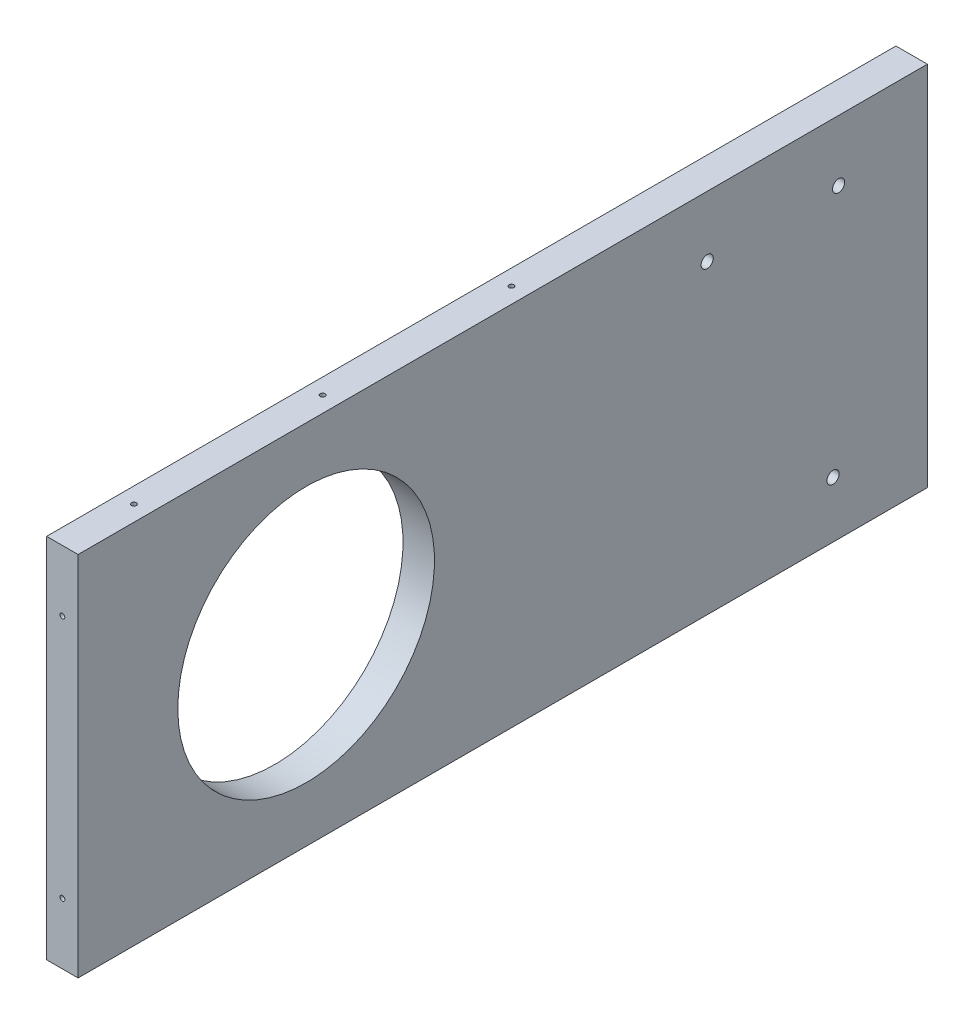
SolidWorks part; units mm, degrees
material "MDF"
ref_plane "Front Plane" through (0, 0, 0) normal (0, 0, 1) x (1, 0, 0)
ref_plane "Top Plane" through (0, 0, 0) normal (0, 1, 0) x (1, 0, 0)
ref_plane "Right Plane" through (0, 0, 0) normal (1, 0, 0) x (0, 0, -1)
sketch "Sketch1" plane through (0, 0, 0) normal (0, 0, 1) x (1, 0, 0)
  line L0 (-272.8912, -3.175) -> (-450.3737, -3.175) construction
  line L1 (-438.8802, -3.175) -> (-451.5802, -3.175)
  line L2 (-438.8802, -3.175) -> (-438.8802, -151.2545)
  line L3 (-438.8802, -151.2545) -> (-451.5802, -151.2545)
  line L4 (-451.5802, -3.175) -> (-451.5802, -151.2545)
  line L6 (-450.3737, -152.2395) -> (-393.0861, -199.0142) construction
  line L8 (-451.5802, -20.574) -> (-451.5802, -45.974) construction
  dimension "D1" = 12.7
extrude "Boss-Extrude1" add sketch "Sketch1" along normal blind 342.9
hole_wizard "15/64 (0.23438) Diameter Hole1" positions "Sketch2" profile "Sketch3" hole size "15/64" standard "ANSI Inch"
sketch "Sketch2" plane through (-183.6737, 1933.3759, -6.35) normal (0, 0, -1) x (1, 0, 0)
  point P0 (-261.5565, 1973.5707)
  point P3 (-261.5565, 2010.5906)
  point P6 (-261.5565, 2047.6104)
  point P9 (-97.5233, 2112.4817)
  point P12 (-97.5233, 2147.6884)
  point P15 (-43.3641, 2120.0659)
  point P18 (1.27, 2120.0659)
  point P21 (45.9041, 2120.0659)
  point P24 (100.0633, 2147.6884)
  point P27 (100.0633, 2112.4817)
  point P30 (264.0965, 2047.6104)
  point P33 (264.0965, 1973.5707)
sketch "Sketch3" plane through (-445.2302, -40.1949, -6.35) normal (1, 0, 0) x (0, 1, 0)
  line L0 (0, 0) -> (0, 14.4885)
  line L1 (0, 14.4885) -> (2.9766, 12.7)
  line L2 (2.9766, 12.7) -> (2.9766, 0)
  line L3 (2.9766, 0) -> (0, 0)
  line L4 (0, 14.4885) -> (-2.9766, 12.7) construction
  line L5 (0, -6.35) -> (0, 107.95) construction
  dimension "Hole Dia." = 5.9533
  dimension "Hole Depth" = 12.7
  dimension "Drill Angle" = 118
hole_wizard "15/64 (0.23438) Diameter Hole3" positions "Sketch6" profile "Sketch7" hole size "15/64" standard "ANSI Inch"
sketch "Sketch6" plane through (-182.4037, 1936.854, -6.35) normal (0, 0, -1) x (1, 0, 0)
  point P0 (-262.8265, 2051.0885)
  point P3 (-262.8265, 2014.0687)
  point P6 (-262.8265, 1977.0488)
  point P9 (-98.7933, 2115.9598)
  point P12 (-98.7933, 2151.1665)
  point P15 (-44.6341, 2123.544)
  point P18 (0, 2123.544)
  point P21 (44.6341, 2123.544)
sketch "Sketch7" plane through (-445.2302, -114.2346, -6.35) normal (1, 0, 0) x (0, 1, 0)
  line L0 (0, 0) -> (0, 20.8385)
  line L1 (0, 20.8385) -> (2.9766, 19.05)
  line L2 (2.9766, 19.05) -> (2.9766, 0)
  line L3 (2.9766, 0) -> (0, 0)
  line L4 (0, 20.8385) -> (-2.9766, 19.05) construction
  line L5 (0, -6.35) -> (0, 107.95) construction
  dimension "Hole Dia." = 5.9533
  dimension "Hole Depth" = 19.05
  dimension "Drill Angle" = 118
hole_wizard "5/64 (0.07813) Diameter Hole1" positions "Sketch8" profile "Sketch9" hole size "5/64" standard "ANSI Inch"
sketch "Sketch8" plane through (-182.4037, 15.875, 6471.4599) normal (0, 1, 0) x (1, 0, 0)
  line L1 (-1.27, 6109.5099) -> (-1.27, 6338.7449) construction
  point P0 (-262.8265, 6157.4524)
  point P6 (-98.7933, 6157.4524)
  point P18 (-262.8265, 6233.6524)
  point P19 (-98.7933, 6233.6524)
  point P22 (-262.8265, 6309.8524)
  point P23 (-98.7933, 6309.8524)
  point P24 (-267.97, 6119.0349)
  point P34 (-115.57, 6119.0349)
  point P37 (-1.27, 6119.0349)
  point P40 (113.03, 6119.0349)
  point P44 (265.43, 6119.0349)
  point P55 (96.2533, 6309.8524)
  point P56 (260.2865, 6309.8524)
  point P59 (96.2533, 6233.6524)
  point P60 (260.2865, 6233.6524)
  point P63 (96.2533, 6157.4524)
  point P64 (260.2865, 6157.4524)
sketch "Sketch9" plane through (-445.2302, 15.875, 314.0075) normal (1, 0, 0) x (0, 0, 1)
  line L0 (0, 0) -> (0, 38.6962)
  line L1 (0, 38.6962) -> (0.9923, 38.1)
  line L2 (0.9923, 38.1) -> (0.9923, 4.7024)
  line L3 (0.9923, 4.7024) -> (5.08, 0)
  line L4 (5.08, 0) -> (0, 0)
  line L5 (-0.9923, 4.7024) -> (-5.08, 0) construction
  line L6 (0, 38.6962) -> (-0.9923, 38.1) construction
  line L7 (0, -6.35) -> (0, 107.95) construction
  dimension "Hole Dia." = 1.9845
  dimension "Hole Depth" = 38.1
  dimension "Near C'Sink Dia." = 10.16
  dimension "Near C'Sink Angle" = 82
  dimension "Drill Angle" = 118
hole_wizard "5/64 (0.07813) Diameter Hole2" positions "Sketch10" profile "Sketch11" hole size "5/64" standard "ANSI Inch"
sketch "Sketch10" plane through (-182.4037, 1936.854, 361.95) normal (0, 0, 1) x (-1, 0, 0)
  line L23 (262.8265, 2088.1084) -> (262.8265, 2038.7486)
  line L24 (262.8265, 2038.7486) -> (262.8265, 1989.3888)
  line L25 (262.8265, 1989.3888) -> (262.8265, 2038.7486)
  line L26 (262.8265, 2038.7486) -> (262.8265, 1989.3888)
  line L27 (262.8265, 1989.3888) -> (262.8265, 1940.029)
  line L33 (98.7933, 2170.2165) -> (98.7933, 2131.8519)
  line L35 (98.7933, 2131.8519) -> (98.7933, 2093.4873)
  line L36 (98.7933, 2093.4873) -> (98.7933, 2055.1227)
  line L37 (98.7933, 2055.1227) -> (98.7933, 2016.7581)
  line L38 (98.7933, 2016.7581) -> (98.7933, 1978.3935)
  line L39 (98.7933, 1978.3935) -> (98.7933, 1940.029)
  line L44 (89.2683, 2123.544) -> (53.561, 2123.544)
  line L46 (53.561, 2123.544) -> (17.8537, 2123.544)
  line L47 (17.8537, 2123.544) -> (-17.8537, 2123.544)
  line L48 (-17.8537, 2123.544) -> (-53.561, 2123.544)
  line L49 (-53.561, 2123.544) -> (-89.2683, 2123.544)
  line L53 (0, 2170.2165) -> (0.2777, 1940.029) construction
  line L55 (-98.3301, 1978.1557) -> (-98.2375, 1939.7912)
  line L56 (-98.4227, 2016.5202) -> (-98.3301, 1978.1557)
  line L57 (-98.5153, 2054.8846) -> (-98.4227, 2016.5202)
  line L58 (-98.6078, 2093.2491) -> (-98.5153, 2054.8846)
  line L59 (-98.7004, 2131.6136) -> (-98.6078, 2093.2491)
  line L60 (-98.793, 2169.978) -> (-98.7004, 2131.6136)
  line L61 (-262.3894, 1988.755) -> (-262.2702, 1939.3954)
  line L62 (-262.5085, 2038.1147) -> (-262.3894, 1988.755)
  line L63 (-262.3894, 1988.755) -> (-262.5085, 2038.1147)
  line L64 (-262.5085, 2038.1147) -> (-262.3894, 1988.755)
  line L65 (-262.6276, 2087.4744) -> (-262.5085, 2038.1147)
  point P71 (262.8265, 1964.7089)
  point P79 (262.8265, 2063.4285)
  point P95 (98.7933, 2131.8519)
  point P103 (98.7933, 1978.3935)
  point P126 (53.561, 2123.544)
  point P134 (-53.561, 2123.544)
  point P162 (-98.3301, 1978.1557)
  point P166 (-98.7004, 2131.6136)
  point P167 (-262.568, 2062.7945)
  point P169 (-262.3298, 1964.0752)
sketch "Sketch11" plane through (79.926, -27.2212, 361.95) normal (1, 0, 0) x (0, -1, 0)
  line L0 (0, 0) -> (0, 38.6962)
  line L1 (0, 38.6962) -> (0.9923, 38.1)
  line L2 (0.9923, 38.1) -> (0.9923, 4.7024)
  line L3 (0.9923, 4.7024) -> (5.08, 0)
  line L4 (5.08, 0) -> (0, 0)
  line L5 (-0.9923, 4.7024) -> (-5.08, 0) construction
  line L6 (0, 38.6962) -> (-0.9923, 38.1) construction
  line L7 (0, -6.35) -> (0, 107.95) construction
  dimension "Hole Dia." = 1.9845
  dimension "Hole Depth" = 38.1
  dimension "Near C'Sink Dia." = 10.16
  dimension "Near C'Sink Angle" = 82
  dimension "Drill Angle" = 118
hole_wizard "#8 Clearance Hole1" positions "Sketch12" profile "Sketch13" hole size "#8" standard "ANSI Inch" end condition up to next
sketch "Sketch12" plane through (-451.5802, 0, 0) normal (-1, 0, 0) x (0, 0, 1)
  point P0 (88.9, -27.7495)
  point P2 (35.8275, -27.7495)
  point P4 (38.1, -128.5875)
sketch "Sketch13" plane through (-451.5802, -27.7495, 88.9) normal (0, 1, 0) x (0, 0, 1)
  line L0 (0, 0) -> (0, 12.7)
  line L1 (0, 12.7) -> (2.4574, 12.7)
  line L2 (2.4574, 12.7) -> (2.4574, 0)
  line L5 (2.4574, 0) -> (0, 0)
  line L11 (0, -6.35) -> (0, 107.95) construction
  dimension "Thru Hole Dia." = 4.9149
  dimension "Thru Hole Depth" = 12.7
sketch "Sketch14" plane through (-451.5802, 0, 0) normal (-1, 0, 0) x (0, 0, 1)
  line L0 (158.75, -33.3375) -> (342.9, -33.3375) construction
  line L1 (158.75, -53.975) -> (158.75, -12.7) construction
  line L2 (342.9, -3.175) -> (342.9, -151.2545) construction
  line L3 (250.825, -151.2545) -> (250.825, -3.175) construction
  line L4 (342.9, -151.2545) -> (0, -151.2545) construction
  line L5 (132.715, -3.175) -> (361.95, -3.175) construction
  circle A0 centre (250.825, -77.2147) radius 51.8147
  point P6 (250.825, -33.3375)
  point P13 (250.825, -77.2147)
  point P16 (250.825, -129.0295)
  dimension "D1" = 22.225
extrude "Cut-Extrude1" cut sketch "Sketch14" against normal up to next
